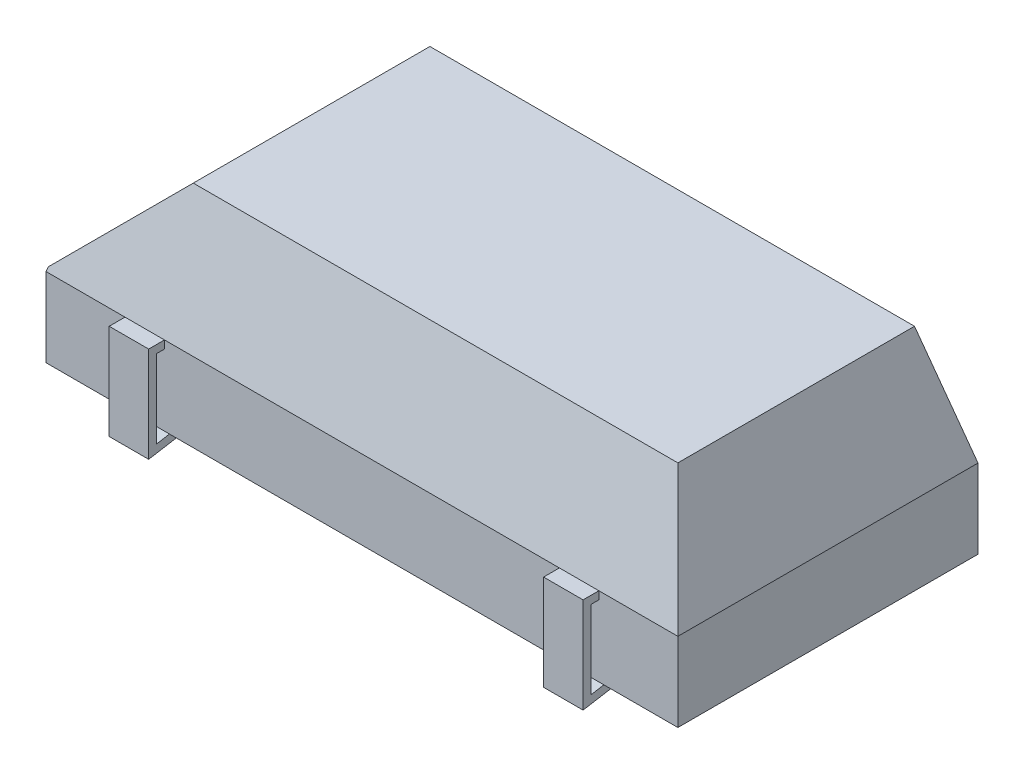
SolidWorks part; units mm, degrees
ref_plane "Front Plane" through (0, 0, 0) normal (0, 0, 1) x (1, 0, 0)
ref_plane "Top Plane" through (0, 0, 0) normal (0, 1, 0) x (1, 0, 0)
ref_plane "Right Plane" through (0, 0, 0) normal (1, 0, 0) x (0, 0, -1)
sketch "Sketch1" plane through (0, 0, 0) normal (0, 1, 0) x (1, 0, 0)
  line L1 (-4, -1.9) -> (4, -1.9)
  line L2 (-4, -1.9) -> (-4, 1.9)
  line L3 (-4, 1.9) -> (4, 1.9)
  line L4 (4, -1.9) -> (4, 1.9)
  line L5 (-4, -1.9) -> (4, 1.9) construction
  line L6 (-4, 1.9) -> (4, -1.9) construction
  point P0 (0, 0)
  dimension "D1" = 8
  dimension "D2" = 3.8
extrude "Boss-Extrude1" add sketch "Sketch1" along normal blind 2.5
chamfer "Chamfer1" distance 1.5 angle 15 4 edges at (-4, 2.5, 0) (0, 2.5, -1.9) (4, 2.5, 0) (0, 2.5, 1.9) first distance on face at (-4, 1.25, 0) first distance on face at (0, 1.25, -1.9) first distance on face at (4, 1.25, 0) first distance on face at (0, 1.25, 1.9)
chamfer "Chamfer2" distance 1.5 angle 30 1 edges at (-3.5981, 2.5, 0) first distance on face at (-3.799, 1.75, 0)
sketch "Sketch2" plane through (0, 0, 1.9) normal (0, 0, 1) x (1, 0, 0)
  line L0 (0, 0) -> (0, 2.552) construction
  line L1 (0, 1) -> (-2.75, 1) construction
  line L2 (4, 1) -> (-4, 1) construction
  line L3 (-3, 0.9) -> (-3, 1)
  line L4 (-3, 0.9) -> (-2.5, 0.9)
  line L5 (-3, 1) -> (-2.5, 1)
  line L6 (-2.5, 0.9) -> (-2.5, 1)
  line L7 (-3, 0.9) -> (-2.5, 1) construction
  line L8 (-3, 1) -> (-2.5, 0.9) construction
  point P8 (-2.75, 0.95)
  dimension "D1" = 0.1
  dimension "D2" = 0.5
ref_plane "Plane1" through (-2.75, 0, 0) normal (1, 0, 0) x (0, 0, -1)
sketch "Sketch3" plane through (-2.75, 0, 0) normal (1, 0, 0) x (0, 0, -1)
  line L0 (-1.9, 0.95) -> (-2.05, 0.95)
  line L1 (-2.05, 0.95) -> (-2.05, -0.15)
  line L3 (-2.05, -0.15) -> (-1.1626, 0)
  line L4 (1.9, 0) -> (-1.9, 0) construction
  dimension "D1" = 0.15
  dimension "D2" = 1.1
  dimension "D3" = 0.9
sweep "Sweep1" add profiles "Sketch2" path "Sketch3"
ref_axis "Axis1" through (0, -0.3447, 0) along (0, 1, 0)
pattern_linear "LPattern1" count 2 spacing 5.5 along (1, 0, 0) of "Sweep1"
mirror "Mirror1" about plane through (0, 0, 0) normal (0, 0, 1) of "LPattern1"
